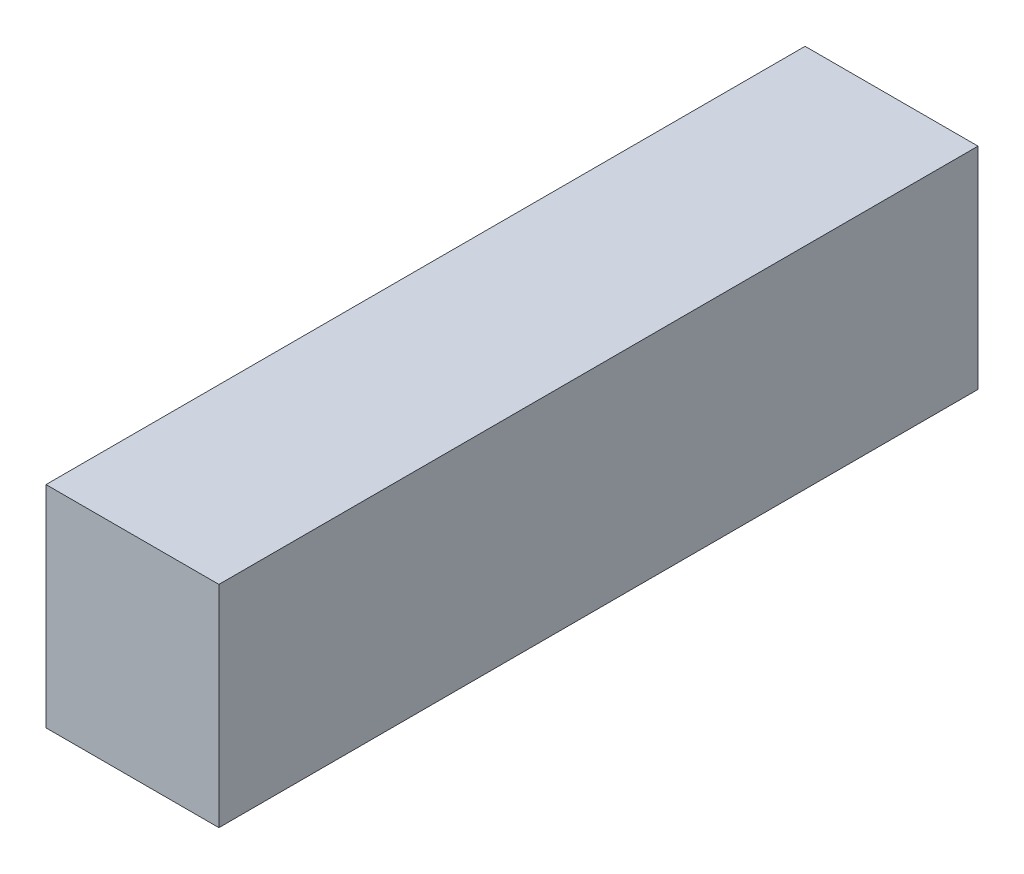
SolidWorks part; units mm, degrees
ref_plane "Front Plane" through (0, 0, 0) normal (0, 0, 1) x (1, 0, 0)
ref_plane "Top Plane" through (0, 0, 0) normal (0, 1, 0) x (1, 0, 0)
ref_plane "Right Plane" through (0, 0, 0) normal (1, 0, 0) x (0, 0, -1)
sketch "Sketch1" plane through (0, 0, 0) normal (1, 0, 0) x (0, 0, -1)
  line L1 (-48.895, 25.4386) -> (82.8131, 25.4386)
  line L2 (-48.895, 25.4386) -> (-48.895, -11.1225)
  line L3 (-48.895, -11.1225) -> (82.8131, -11.1225)
  line L4 (82.8131, 25.4386) -> (82.8131, -11.1225)
extrude "Boss-Extrude1" add sketch "Sketch1" along normal blind 30
shell "Shell1" thickness 10
